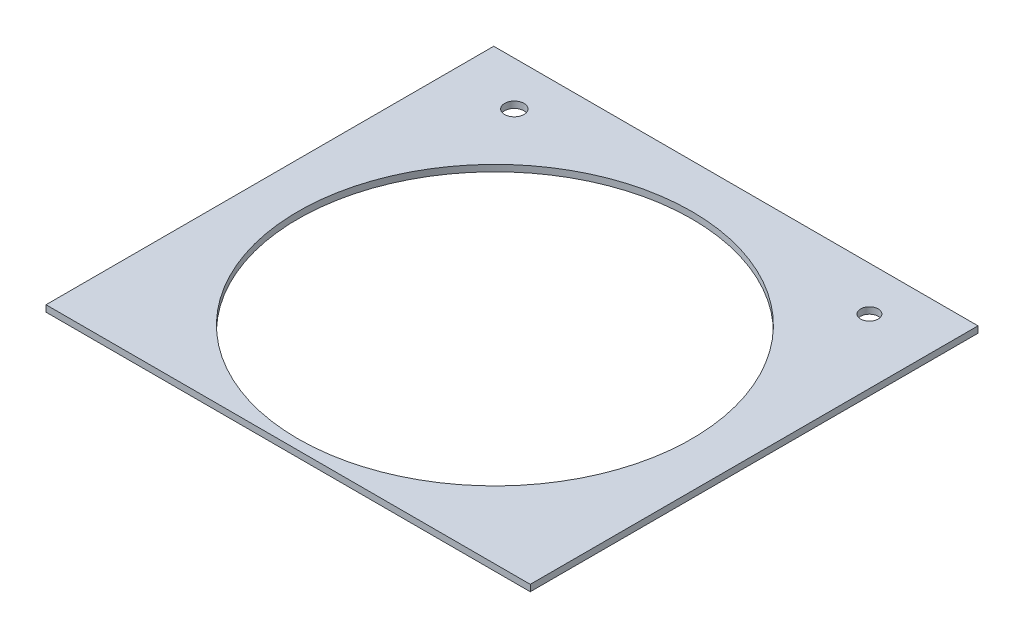
SolidWorks part; units mm, degrees
ref_plane "Front Plane" through (0, 0, 0) normal (0, 0, 1) x (1, 0, 0)
ref_plane "Top Plane" through (0, 0, 0) normal (0, 1, 0) x (1, 0, 0)
ref_plane "Right Plane" through (0, 0, 0) normal (1, 0, 0) x (0, 0, -1)
sketch "Sketch1" plane through (0, 0, 0) normal (0, 1, 0) x (1, 0, 0)
  line L3 (-37.5, 34.8346) -> (37.5, 34.8346)
  line L4 (37.5, -34.51) -> (37.5, 34.8346)
  line L5 (-37.5, -34.51) -> (37.5, -34.51)
  line L11 (-37.5, 34.8346) -> (-37.5, -34.51)
  circle A0 centre (-27.5, 28.0164) radius 1.5
  circle A1 centre (27.5, 28.0164) radius 1.3636
  circle A4 centre (0, -2.4836) radius 30.5
  point P0 (0, 0)
  point P5 (0, 0)
  point P16 (0, 28.0164)
  dimension "D1" = 75
  dimension "D2" = 55
extrude "Boss-Extrude1" add sketch "Sketch1" along normal blind 1
